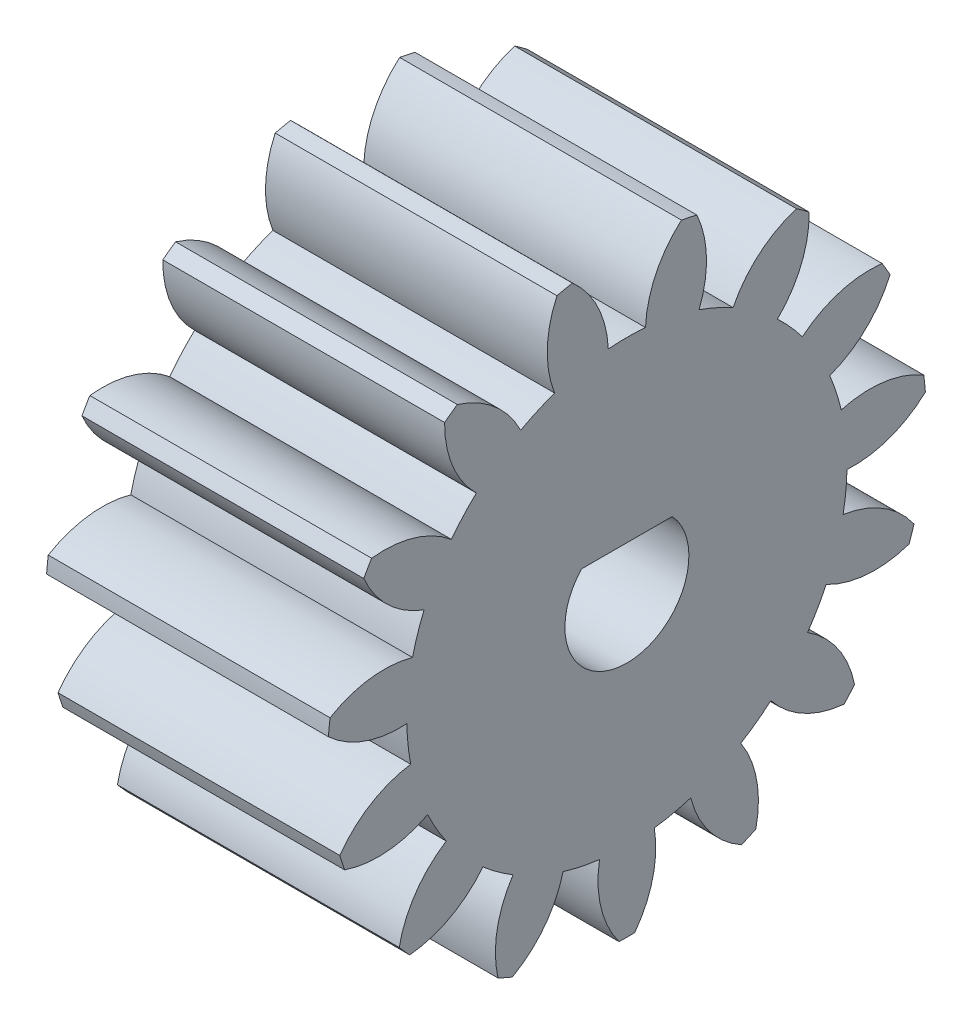
SolidWorks part; units mm, degrees
ref_plane "Plane1" through (0, 0, 0) normal (0, 0, 1) x (1, 0, 0)
ref_plane "Plane2" through (0, 0, 0) normal (0, 1, 0) x (1, 0, 0)
ref_plane "Plane3" through (0, 0, 0) normal (1, 0, 0) x (0, 0, -1)
sketch "HoldingSke" plane through (0, 0, 0) normal (0, 1, 0) x (1, 0, 0)
  line L0 (0, 0) -> (0.7727, -0.2071)
  line L1 (-15, 0) -> (100, 0) construction
  line L2 (0, 0) -> (-2.1039, 2.3779)
  line L3 (0, 0) -> (-11.863, 4.5341)
  line L4 (0, 0) -> (8.3417, 2.2352)
  line L5 (0, 0) -> (-46.8476, -17.4728)
  line L6 (0, 0) -> (-8.2896, -5.593)
  line L7 (-2.1039, 2.3779) -> (8.6586, 51.2059)
  line L8 (-76.2, 54.61) -> (-75.5, 54.61)
  line L9 (-71.009, 38.7566) -> (-53.1078, 45.2721)
  line L10 (-76.2, 71.12) -> (104.1128, 71.12)
  line L11 (0, 0) -> (-10, 0)
  line L12 (-76.2, 101.6) -> (-76.155, 101.6)
  line L13 (24.9733, 27.94) -> (52.9518, 28.4284)
  line L14 (24.9733, 27.94) -> (24.9743, 27.94)
  line L15 (24.9733, 27.94) -> (100.4006, 29.5858)
  line L16 (-63.627, -1.25) -> (-12.827, -1.25)
  circle A0 centre (0, 0) radius 2
  circle A1 centre (0, 0) radius 7.8115
  circle A2 centre (0, 0) radius 37.5
  circle A3 centre (0, 0) radius 2
  dimension "MHD" = 15.623
  dimension "Hub_dia" = 75
  dimension "Bore" = 4
  dimension "MBD" = 4
  dimension "Num_teeth" = 15
  dimension "Pitch" = 0.8
  dimension "Overall_len" = 50
  dimension "Show_teeth" = 15
  dimension "Thickness" = 10
  dimension "OAL" = 50.0001
  dimension "T_dim" = 0.7
  dimension "Ap" = 20
  dimension "H" = 19.05
  dimension "Pitch_radius" = 180.3128
  dimension "Width" = 10
  dimension "Backlash" = 0.045
  dimension "Addendum_fac" = 1
  dimension "Dedendum_fac" = 1.25
  dimension "Clearance_fac" = 0.25
  dimension "Dedendum_add" = 0.001
  dimension "Module" = 1.25
sketch "BasProSke" plane through (0, 0, 0) normal (0, 1, 0) x (1, 0, 0)
  line L0 (-10, 0) -> (60, 0) construction
  line L1 (0, 0) -> (0, 10.625)
  line L2 (0, 0) -> (10, 0)
  line L3 (10, 0) -> (10, 10.625)
  line L4 (10, 10.625) -> (0, 10.625)
  dimension "Thickness" = 10
  dimension "Diameter" = 21.25
revolve "Base-Revolve" add sketch "BasProSke" angle 360 about L0
sketch "TooCutSke" plane through (0, 0, 0) normal (1, 0, 0) x (0, 0, -1)
  line L1 (0, 0) -> (0, 107) construction
  line L2 (0, 0) -> (-1.0586, 9.315) construction
  line L3 (0, 0) -> (-3.8803, 18.2553) construction
  line L4 (-1.0586, 9.315) -> (-1.9401, 9.1277) construction
  arc A0 (0.6608, 7.7835) -> (-0.6608, 7.7835) centre (0, 0) ccw
  arc A1 (1.9597, 10.4686) -> (-1.9597, 10.4686) centre (0, 0) ccw
  circle A2 centre (0, 0) radius 9.375 construction
  circle A3 centre (0, 0) radius 8.8096 construction
  arc A4 (-0.6608, 7.7835) -> (-1.9597, 10.4686) centre (-4.4076, 7.6277) ccw
  arc A5 (1.9597, 10.4686) -> (0.6608, 7.7835) centre (4.4076, 7.6277) ccw
  dimension "Root_dia" = 15.623
  dimension "Overcut_dia" = 21.3008
  dimension "Pitch_dia" = 18.75
  dimension "Base_dia" = 17.6192
  dimension "Flank_rad" = 3.75
  dimension "Half_ang" = 12
  dimension "Half_CT" = 0.9012
extrude "ToothCut" cut sketch "TooCutSke" along normal through all
fillet "Breaks" [suppressed] radius 0.025 tangent propagation no
fillet "RootFillets" [suppressed] radius 0.3135
pattern_circular "TeethCuts" count 15 every 24 about axis through (-10, 0, 0) along (1, 0, 0) of "ToothCut", "RootFillets", "Breaks"
sketch "HubNeaOneSke" plane through (0, 0, 0) normal (-1, 0, 0) x (0, 0, 1)
  circle A0 centre (0, 0) radius 7.8115
  dimension "Diameter" = 15.623
extrude "HubNearOne" [suppressed] add sketch "HubNeaOneSke" along normal blind 40.0001
sketch "HubNeaBotSke" plane through (0, 0, 0) normal (-1, 0, 0) x (0, 0, 1)
  circle A0 centre (0, 0) radius 7.8115
  dimension "Diameter" = 15.623
extrude "HubNearBoth" [suppressed] add sketch "HubNeaBotSke" along normal blind 20
ref_plane "FarPln" through (10, 0, 0) normal (1, 0, 0) x (0, 0, -1)
sketch "HubFarSke" plane through (10, 0, 0) normal (1, 0, 0) x (0, 0, -1)
  circle A0 centre (0, 0) radius 7.8115
  dimension "Diameter" = 15.623
extrude "HubFar" [suppressed] add sketch "HubFarSke" along normal blind 20
sketch "BorSke" plane through (0, 0, 0) normal (1, 0, 0) x (0, 0, -1)
  circle A0 centre (0, 0) radius 2
  dimension "Diameter" = 4
extrude "Bore" cut sketch "BorSke" along normal mid plane 100.0001
sketch "KeySke" plane through (0, 0, 0) normal (1, 0, 0) x (0, 0, -1)
  line L0 (-0.8, 0) -> (-0.8, 2.7)
  line L1 (-0.8, 2.7) -> (0.8, 2.7)
  line L2 (0.8, 2.7) -> (0.8, 0)
  line L3 (0, 0) -> (0, 34) construction
  line L4 (-0.8, 0) -> (0.8, 0)
  dimension "Offset" = 2.7
  dimension "Width" = 1.6
extrude "Keyway" [suppressed] cut sketch "KeySke" along normal mid plane 100.0001
pattern_circular "Keyway2" [suppressed] count 2 every 90 about axis through (-10, 0, 0) along (1, 0, 0) reverse direction yes
sketch "Sketch1" plane through (10, 0, 0) normal (1, 0, 0) x (0, 0, -1)
  circle A0 centre (0, 0) radius 2.2
  dimension "D1" = 4.4
extrude "Cut-Extrude2" cut sketch "Sketch1" against normal blind 10
sketch "Sketch4" plane through (10, 0, 0) normal (1, 0, 0) x (0, 0, -1)
  line L0 (0, -2.2) -> (0, 1.5) construction
  line L1 (-1.6093, 1.5) -> (1.6093, 1.5)
  circle A0 centre (0, 0) radius 2.2 construction
  arc A1 (-1.6093, 1.5) -> (1.6296, 1.4779) centre (0, 0) cw
extrude "Boss-Extrude1" add sketch "Sketch4" against normal blind 10 contours A1 L1 region at (10, 1.7842, 0)
equation "' \"Module@HoldingSke\" = 6.35"
equation "' \"Num_teeth@HoldingSke\" = 12"
equation "' \"Ap@HoldingSke\" =  20"
equation "' \"Ap@HoldingSke\" = 20"
equation "' \"Width@HoldingSke\" = 0.5 * 25.4"
equation "' \"Hub_dia@HoldingSke\"= 1 * 25.4"
equation "' \"Hub_dia@HoldingSke\" = 1 * 25.4"
equation "' \"Overall_len@HoldingSke\" = 1.0 * 25.4"
equation "' \"Bore@HoldingSke\" = 0.75 * 25.4"
equation "' \"T_dim@HoldingSke\" = 0.1 * 25.4"
equation "' \"Width@KeySke\" = 0.25 * 25.4"
equation "' \"Show_teeth@HoldingSke\" = 13"
equation "' \"Backlash@HoldingSke\" = 0.009 * 25.4"
equation "' \"Addendum_fac@HoldingSke\" = 1.0"
equation "' \"Dedendum_fac@HoldingSke\" = 1.25"
equation "' \"Dedendum_add@HoldingSke\" = 0.00005 * 25.4"
equation "' \"Clearance_fac@HoldingSke\" = 0.25"
equation "\"Pitch@HoldingSke\" = 1 / \"Module@HoldingSke\""
equation "\"Overcut_dia@TooCutSke\" = (\"Num_teeth@HoldingSke\" + 2 * \"Addendum_fac@HoldingSke\") / \"Pitch@HoldingSke\" + 0.002 * 25.4"
equation "\"Pitch_dia@TooCutSke\" = \"Num_teeth@HoldingSke\" / \"Pitch@HoldingSke\""
equation "\"Base_dia@TooCutSke\" = \"Num_teeth@HoldingSke\" / \"Pitch@HoldingSke\" * cos((\"Ap@HoldingSke\"  * 3.14159265 / 180))"
equation "\"Root_dia@TooCutSke\" = (\"Num_teeth@HoldingSke\" + 2) / \"Pitch@HoldingSke\" - 2 * (\"Addendum_fac@HoldingSke\" + \"Dedendum_fac@HoldingSke\") / \"Pitch@HoldingSke\" - \"Dedendum_add@HoldingSke\" * 2"
equation "\"Half_ang@TooCutSke\" = 180 / \"Num_teeth@HoldingSke\""
equation "\"Half_CT@TooCutSke\" = \"Num_teeth@HoldingSke\" / \"Pitch@HoldingSke\" * sin((3.14159265 / 2 / \"Num_teeth@HoldingSke\")) / 2 - 7 * \"Backlash@HoldingSke\" / 4"
equation "\"Flank_rad@TooCutSke\" = \"Num_teeth@HoldingSke\" / \"Pitch@HoldingSke\" / 5"
equation "\"Radius@RootFillets\" = \"Clearance_fac@HoldingSke\" / \"Pitch@HoldingSke\" + \"Dedendum_add@HoldingSke\""
equation "\"Break_rad@Breaks\" = 0.02 / \"Pitch@HoldingSke\""
equation "\"Thickness@HoldingSke\" = \"Width@HoldingSke\""
equation "\"OAL@HoldingSke\" = \"Thickness@HoldingSke\""
equation "\"MHD@HoldingSke\" = (\"Num_teeth@HoldingSke\" + 2) / \"Pitch@HoldingSke\" - 2 * (\"Addendum_fac@HoldingSke\" + \"Dedendum_fac@HoldingSke\")  / \"Pitch@HoldingSke\" - \"Dedendum_add@HoldingSke\" * 2"
equation "\"MBD@HoldingSke\" = (\"Num_teeth@HoldingSke\" + 2) / \"Pitch@HoldingSke\" - 2 * (\"Addendum_fac@HoldingSke\" + \"Dedendum_fac@HoldingSke\")  / \"Pitch@HoldingSke\" - \"Dedendum_add@HoldingSke\" * 2 - 0.002 * 25.4"
equation "\"MHD@HoldingSke\" = ((sgn( \"MHD@HoldingSke\" - \"Hub_dia@HoldingSke\" )-1)*( \"MHD@HoldingSke\" - \"Hub_dia@HoldingSke\" ))/-2+ \"Hub_dia@HoldingSke\""
equation "\"MBD@HoldingSke\" = ((sgn( \"MBD@HoldingSke\" - \"Bore@HoldingSke\" )-1)*( \"MBD@HoldingSke\" - \"Bore@HoldingSke\" ))/-2+ \"Bore@HoldingSke\""
equation "\"OAL@HoldingSke\" = ((sgn( \"OAL@HoldingSke\" - \"Overall_len@HoldingSke\" )+1)*( \"OAL@HoldingSke\" - \"Overall_len@HoldingSke\" ))/2 + \"Overall_len@HoldingSke\" + 0.000002 * 25.4"
equation "\"Num_teeth@TeethCuts\" = int( \"Show_teeth@HoldingSke\" ) + 1"
equation "\"Num_teeth@TeethCuts\" = ((sgn( \"Num_teeth@TeethCuts\" - \"Num_teeth@HoldingSke\" )-1)*( \"Num_teeth@TeethCuts\" - \"Num_teeth@HoldingSke\" ))/-2+ \"Num_teeth@HoldingSke\""
equation "\"Num_teeth@TeethCuts\" = ((sgn( \"Num_teeth@TeethCuts\" - 2.0)+1)*( \"Num_teeth@TeethCuts\" - 2.0))/2 +2.0"
equation "\"Angle@TeethCuts\" = 360.0 / \"Num_teeth@HoldingSke\""
equation "\"Diameter@BasProSke\" = (\"Num_teeth@HoldingSke\" + 2 * \"Addendum_fac@HoldingSke\") / \"Pitch@HoldingSke\""
equation "\"Thickness@BasProSke\"  = \"Thickness@HoldingSke\""
equation "' \"Fillet_rad@BasProSke\" =  \"Thickness@HoldingSke\" * 0.05"
equation "' \"Fillet_rad@BasProSke\" = \"Thickness@HoldingSke\" * 0.05"
equation "\"MHD@HoldingSke\" = ((sgn( \"MHD@HoldingSke\" - \"Root_dia@TooCutSke\" )-1)*( \"MHD@HoldingSke\" - \"Root_dia@TooCutSke\" ))/-2+ \"Root_dia@TooCutSke\""
equation "\"Diameter@HubNeaOneSke\" = \"MHD@HoldingSke\""
equation "\"Length@HubNearOne\" = \"OAL@HoldingSke\" - \"Thickness@BasProSke\""
equation "\"Diameter@HubNeaBotSke\" = \"MHD@HoldingSke\""
equation "\"Length@HubNearBoth\" = ( \"OAL@HoldingSke\" - \"Thickness@BasProSke\" ) / 2.0"
equation "\"Thickness@FarPln\" = \"Thickness@BasProSke\""
equation "\"Diameter@HubFarSke\" = \"MHD@HoldingSke\""
equation "\"Length@HubFar\" = ( \"OAL@HoldingSke\" - \"Thickness@BasProSke\" ) / 2.0"
equation "\"Diameter@BorSke\" = \"MBD@HoldingSke\""
equation "\"D1@Bore\" = \"OAL@HoldingSke\" * 2.0"
equation "\"D1@Keyway\" = \"OAL@HoldingSke\" * 2.0"
equation "\"Offset@KeySke\" = \"T_dim@HoldingSke\" + \"MBD@HoldingSke\" / 2.0"
